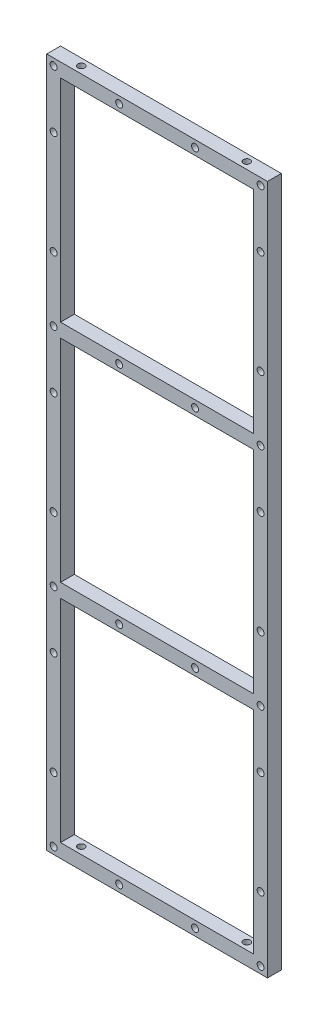
SolidWorks part; units mm, degrees
ref_plane "Front Plane" through (0, 0, 0) normal (0, 0, 1) x (1, 0, 0)
ref_plane "Top Plane" through (0, 0, 0) normal (0, 1, 0) x (1, 0, 0)
ref_plane "Right Plane" through (0, 0, 0) normal (1, 0, 0) x (0, 0, -1)
sketch "Sketch1" plane through (0, 0, 0) normal (0, 0, 1) x (1, 0, 0)
  line L0 (42, 144) -> (42, 52)
  line L9 (-48, -150) -> (48, -150)
  line L10 (-48, -150) -> (-48, 150)
  line L11 (-48, 150) -> (48, 150)
  line L12 (48, -150) -> (48, 150)
  line L13 (0, -55) -> (0, 55) construction
  line L15 (-42, -144) -> (42, -144)
  line L16 (-42, -144) -> (-42, -52)
  line L17 (-42, 144) -> (42, 144)
  line L21 (-42, 52) -> (42, 52)
  line L23 (-42, 46) -> (42, 46)
  line L25 (-42, -46) -> (42, -46)
  line L27 (-42, -52) -> (42, -52)
  line L33 (42, 46) -> (42, -46)
  line L34 (-42, 52) -> (-42, 144)
  line L35 (-42, -46) -> (-42, 46)
  line L36 (42, -52) -> (42, -144)
  point P0 (0, 0)
  point P4 (0, 150)
  point P6 (0, 0)
  point P20 (0, 0)
  dimension "D1" = 96
  dimension "D2" = 300
  dimension "D3" = 84
  dimension "D4" = 288
  dimension "D5" = 6
  dimension "D6" = 92
  dimension "D7" = 6
  dimension "D8" = 92
  dimension "D9" = 92
  dimension "D10" = 6
  dimension "D11" = 6
extrude "Boss-Extrude1" add sketch "Sketch1" along normal blind 6
sketch "Sketch2" plane through (0, 0, 6) normal (0, 0, 1) x (1, 0, 0)
  line L0 (-48, 150) -> (-42, 144)
  line L1 (42, 144) -> (48, 150)
  line L2 (42, -144) -> (48, -150)
  line L3 (-42, -144) -> (-48, -150)
  circle A0 centre (-45, 147) radius 1.5
  circle A1 centre (45, 147) radius 1.5
  circle A2 centre (45, 49) radius 1.5
  circle A3 centre (45, -49) radius 1.5
  circle A4 centre (45, -147) radius 1.5
  circle A5 centre (-45, 49) radius 1.5
  circle A6 centre (-45, -49) radius 1.5
  circle A7 centre (-45, -147) radius 1.5
  point P18 (45, 147)
  point P19 (-45, -147)
  dimension "D1" = 90
  dimension "D2" = 294
  dimension "D3" = 2
  dimension "D4" = 4
extrude "Cut-Extrude1" cut sketch "Sketch2" against normal blind 6 contours A0 | A1 | A5 | A2 | A6 | A3 | A7 | A4
sketch "Sketch3" plane through (0, 0, 6) normal (0, 0, 1) x (1, 0, 0)
  line L0 (48, 150) -> (-48, 150) construction
  line L1 (0, 150) -> (0, -150)
  line L2 (-48, -150) -> (48, -150) construction
  circle A0 centre (-45, 122) radius 1.5
  circle A1 centre (-45, 77) radius 1.5
  circle A2 centre (45, 122) radius 1.5
  circle A3 centre (45, 77) radius 1.5
  circle A4 centre (45, 24) radius 1.5
  circle A5 centre (45, -21) radius 1.5
  circle A6 centre (45, -74) radius 1.5
  circle A7 centre (45, -119) radius 1.5
  circle A8 centre (-45, 24) radius 1.5
  circle A9 centre (-45, -21) radius 1.5
  circle A10 centre (-45, -74) radius 1.5
  circle A11 centre (-45, -119) radius 1.5
  circle A12 centre (-16.5, 147) radius 1.5
  circle A13 centre (-16.5, 49) radius 1.5
  circle A14 centre (-16.5, -49) radius 1.5
  circle A15 centre (-16.5, -147) radius 1.5
  circle A16 centre (16.5, -147) radius 1.5
  circle A17 centre (16.5, -49) radius 1.5
  circle A18 centre (16.5, 49) radius 1.5
  circle A19 centre (16.5, 147) radius 1.5
  point P9 (0, 150)
  circle M18 centre (-45, -49) radius 1.5
  dimension "D1" = 28
  dimension "D6" = 16.5
  dimension "D2" = 45
  dimension "D3" = 28
  dimension "D4" = 2
  dimension "D5" = 3
  dimension "D7" = 4
extrude "Cut-Extrude2" cut sketch "Sketch3" against normal blind 10 contours A9 | M18 | A14 | A10 | A11 | A15 | A16 | A7 | A6 | A17 | A5 | A3 | A18 | A12 | A0 | A19 | A1 | A13 | A8 | A4 | A2 | A10 | A11 region at (-45, 122, 6) region at (-45, 77, 6) region at (45, 122, 6) region at (45, 77, 6) region at (45, 24, 6) region at (45, -21, 6) region at (45, -74, 6) region at (45, -119, 6) region at (-45, 24, 6) region at (-45, -21, 6) region at (-45, -74, 6) region at (-45, -119, 6) region at (-16.5, 147, 6) region at (-16.5, 49, 6) region at (-16.5, -49, 6) region at (-16.5, -147, 6) region at (16.5, -147, 6) region at (16.5, -49, 6) region at (16.5, 49, 6) region at (16.5, 147, 6) region at (-45, -49, 6)
sketch "Sketch4" plane through (0, 150, 0) normal (0, 1, 0) x (1, 0, 0)
  line L0 (48, 0) -> (-48, 0) construction
  line L1 (-48, -6) -> (-48, 0) construction
  line L2 (0, -55) -> (0, 55) construction
  circle A0 centre (-36, -3) radius 1.5
  circle A1 centre (36, -3) radius 1.5
  dimension "D1" = 3
  dimension "D2" = 12
extrude "Cut-Extrude5" cut sketch "Sketch4" against normal blind 10
mirror "Mirror1" about plane through (0, 0, 0) normal (0, 1, 0) of "Cut-Extrude5"
